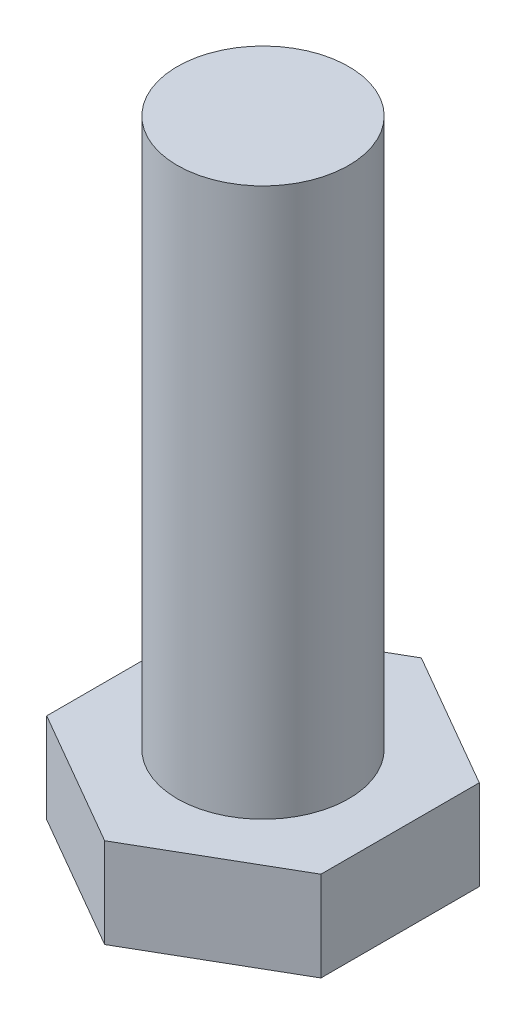
SolidWorks part; units mm, degrees
ref_plane "Спереди" through (0, 0, 0) normal (0, 0, 1) x (1, 0, 0)
ref_plane "Сверху" through (0, 0, 0) normal (0, 1, 0) x (1, 0, 0)
ref_plane "Справа" through (0, 0, 0) normal (1, 0, 0) x (0, 0, -1)
sketch "Эскиз1" plane through (0, 0, 0) normal (0, 1, 0) x (1, 0, 0)
  line L1 (4, -2.3094) -> (4, 2.3094)
  line L2 (4, 2.3094) -> (0, 4.6188)
  line L3 (0, 4.6188) -> (-4, 2.3094)
  line L4 (-4, 2.3094) -> (-4, -2.3094)
  line L5 (-4, -2.3094) -> (0, -4.6188)
  line L6 (0, -4.6188) -> (4, -2.3094)
  circle A0 centre (0, 0) radius 4 construction
extrude "Бобышка-Вытянуть1" add sketch "Эскиз1" along normal blind 3.2
sketch "Эскиз2" plane through (0, 3.2, 0) normal (0, 1, 0) x (1, 0, 0)
  circle A0 centre (0, 0) radius 2.5
extrude "Бобышка-Вытянуть2" add sketch "Эскиз2" along normal blind 16
chamfer "Фаска1" distance 1 angle 30 6 edges at (2, 0, -3.4641) (4, 0, 0) (2, 0, 3.4641) (-2, 0, 3.4641) (-4, 0, 0) (-2, 0, -3.4641) first distance on face at (0, 0, 0)
